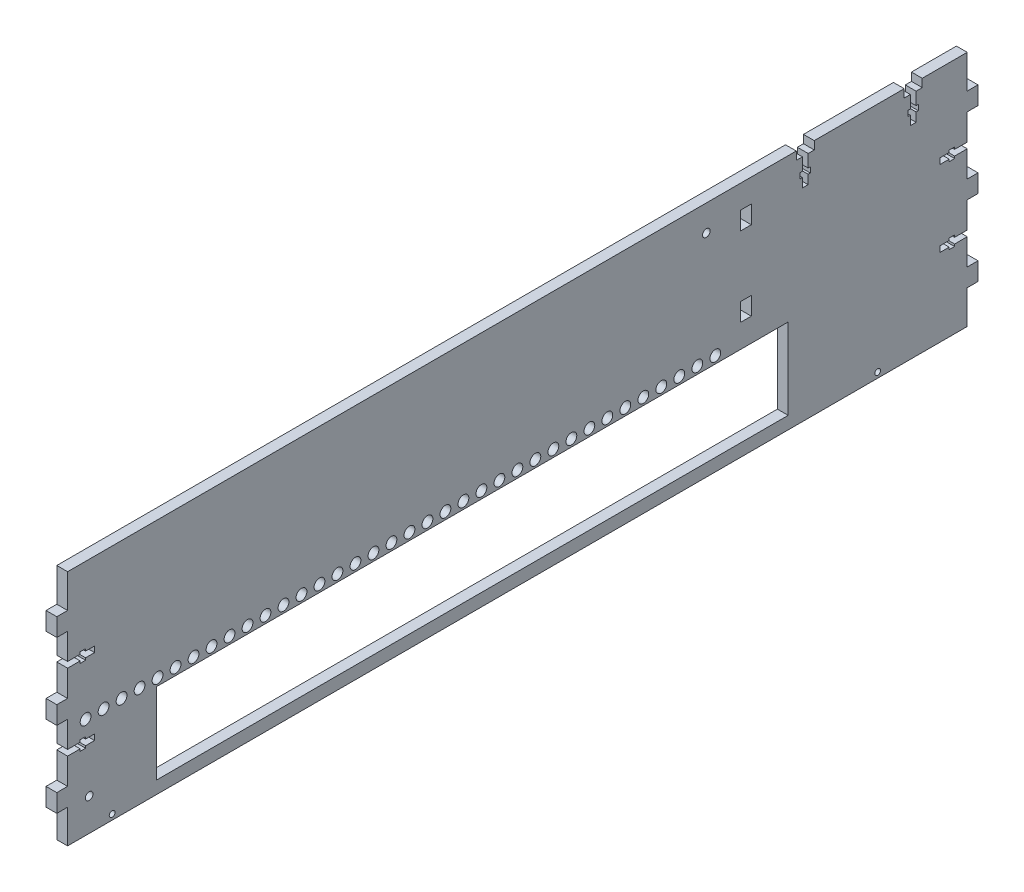
SolidWorks part; units mm, degrees
ref_plane "Front Plane" through (0, 0, 0) normal (0, 0, 1) x (1, 0, 0)
ref_plane "Top Plane" through (0, 0, 0) normal (0, 1, 0) x (1, 0, 0)
ref_plane "Right Plane" through (0, 0, 0) normal (1, 0, 0) x (0, 0, -1)
sketch "Sketch1" plane through (0, 0, 0) normal (1, 0, 0) x (0, 0, -1)
  line L1 (-250, -66) -> (250, -66)
  line L2 (-250, -66) -> (-250, 66)
  line L3 (-250, 66) -> (250, 66)
  line L4 (250, -66) -> (250, 66)
  line L5 (-250, -66) -> (250, 66) construction
  line L6 (-250, 66) -> (250, -66) construction
  point P0 (0, 0)
  dimension "D1" = 132
  dimension "D2" = 500
extrude "Boss-Extrude1" add sketch "Sketch1" along normal blind 6
sketch "Sketch4" plane through (0, 0, 250) normal (0, 0, 1) x (1, 0, 0)
  line L0 (0, 66) -> (0, -66) construction
  line L1 (0, 47.3321) -> (6, 47.3321)
  line L2 (0, 47.3321) -> (0, 37.3321)
  line L3 (0, 37.3321) -> (6, 37.3321)
  line L4 (6, 47.3321) -> (6, 37.3321)
  line L5 (6, 66) -> (6, -66) construction
  line L6 (0, 37.3321) -> (6, 37.3321) construction
  line L7 (0, -66) -> (0, 66) construction
  line L8 (6, 47.3321) -> (0, 47.3321) construction
  line L9 (0, -5) -> (6, -5) construction
  line L10 (0, -5) -> (6, -5)
  line L11 (0, -5) -> (0, 5)
  line L12 (0, 5) -> (6, 5)
  line L13 (6, -5) -> (6, 5)
  line L14 (6, -66) -> (6, 66) construction
  line L15 (6, 5) -> (0, 5) construction
  line L16 (6, -37.3321) -> (0, -37.3321) construction
  line L17 (0, -47.3321) -> (6, -47.3321)
  line L18 (0, -47.3321) -> (0, -37.3321)
  line L19 (0, -37.3321) -> (6, -37.3321)
  line L20 (6, -47.3321) -> (6, -37.3321)
  line L21 (0, -47.3321) -> (6, -47.3321) construction
extrude "Boss-Extrude2" add sketch "Sketch4" along normal blind 6
sketch "Sketch5" plane through (0, 0, 0) normal (-1, 0, 0) x (0, 0, 1)
  line L1 (250, 22.7661) -> (250, 19.5661) construction
  line L3 (250, 22.7661) -> (250, 19.5661) construction
  line L4 (250, -19.5661) -> (250, -22.7661) construction
  line L5 (250, -19.5661) -> (250, -22.7661) construction
  line L6 (250, 21.1661) -> (235, 21.1661) construction
  line L7 (250, -21.1661) -> (235, -21.1661) construction
  line L8 (250, -19.5661) -> (243, -19.5661)
  line L9 (250, 22.7661) -> (243, 22.7661)
  line L10 (250, -22.7661) -> (243, -22.7661)
  line L11 (250, 19.5661) -> (243, 19.5661)
  line L12 (250, -19.5661) -> (250, -22.7661)
  line L13 (235, -19.5661) -> (235, -22.7661)
  line L14 (250, 22.7661) -> (250, 19.5661)
  line L15 (235, 22.7661) -> (235, 19.5661)
  line L16 (240, 19.5661) -> (235, 19.5661)
  line L17 (243, 18.3661) -> (240, 18.3661)
  line L18 (243, 18.3661) -> (243, 19.5661)
  line L19 (243, 23.9661) -> (240, 23.9661)
  line L20 (240, 18.3661) -> (240, 19.5661)
  line L21 (243, 18.3661) -> (240, 23.9661) construction
  line L22 (243, 23.9661) -> (240, 18.3661) construction
  line L23 (243, -23.9661) -> (240, -23.9661)
  line L24 (243, -23.9661) -> (243, -22.7661)
  line L25 (243, -18.3661) -> (240, -18.3661)
  line L26 (240, -23.9661) -> (240, -22.7661)
  line L27 (243, -23.9661) -> (240, -18.3661) construction
  line L28 (243, -18.3661) -> (240, -23.9661) construction
  line L29 (250, 19.5661) -> (235, 19.5661) construction
  line L30 (243, 22.7661) -> (243, 23.9661)
  line L31 (240, 22.7661) -> (235, 22.7661)
  line L32 (250, 22.7661) -> (235, 22.7661) construction
  line L33 (240, 22.7661) -> (240, 23.9661)
  line L34 (240, -19.5661) -> (235, -19.5661)
  line L35 (250, -19.5661) -> (235, -19.5661) construction
  line L36 (240, -19.5661) -> (240, -18.3661)
  line L37 (240, -22.7661) -> (235, -22.7661)
  line L38 (250, -22.7661) -> (235, -22.7661) construction
  line L39 (243, -19.5661) -> (243, -18.3661)
  point P20 (241.5, 21.1661)
  point P25 (241.5, -21.1661)
  line M35 (250, -37.3321) -> (250, -5)
  line M39 (250, 5) -> (250, 37.3321)
  dimension "D3" = 1.6
  dimension "D4" = 7
  dimension "D5" = 3
  dimension "D6" = 5.6
  dimension "D1" = 15
  dimension "D7" = 7
  dimension "D8" = 3
  dimension "D9" = 5.6
  dimension "D2" = 1.6
extrude "Cut-Extrude3" cut sketch "Sketch5" against normal up to next contours L12 | L8 L39 L25 L36 L34 L13 L37 L26 L23 L24 L10 M35 | L33 L31 L15 L16 L20 L17 L18 L11 L9 L30 L19 M39 region at (0, -21.1661, 242.3696) region at (0, 21.1661, 242.3696)
sketch "Sketch6" plane through (0, 0, -250) normal (0, 0, -1) x (-1, 0, 0)
  line L0 (0, 47.3321) -> (0, 37.3321) construction
  line L1 (0, 37.3321) -> (-6, 37.3321) construction
  line L2 (-6, 37.3321) -> (-6, 47.3321) construction
  line L3 (-6, 47.3321) -> (0, 47.3321) construction
  line L4 (0, 5) -> (0, -5) construction
  line L5 (0, -5) -> (-6, -5) construction
  line L6 (-6, -5) -> (-6, 5) construction
  line L7 (-6, 5) -> (0, 5) construction
  line L8 (0, -37.3321) -> (0, -47.3321) construction
  line L9 (0, -47.3321) -> (-6, -47.3321) construction
  line L10 (-6, -47.3321) -> (-6, -37.3321) construction
  line L11 (-6, -37.3321) -> (0, -37.3321) construction
  line L12 (0, 47.3321) -> (0, 37.3321)
  line L13 (0, 37.3321) -> (-6, 37.3321)
  line L14 (-6, 37.3321) -> (-6, 47.3321)
  line L15 (-6, 47.3321) -> (0, 47.3321)
  line L16 (0, 5) -> (0, -5)
  line L17 (0, -5) -> (-6, -5)
  line L18 (-6, -5) -> (-6, 5)
  line L19 (-6, 5) -> (0, 5)
  line L20 (0, -37.3321) -> (0, -47.3321)
  line L21 (0, -47.3321) -> (-6, -47.3321)
  line L22 (-6, -47.3321) -> (-6, -37.3321)
  line L23 (-6, -37.3321) -> (0, -37.3321)
extrude "Boss-Extrude3" add sketch "Sketch6" along normal blind 6
sketch "Sketch7" plane through (0, 0, 0) normal (-1, 0, 0) x (0, 0, 1)
  line L0 (243, 19.5661) -> (250, 19.5661) construction
  line L2 (243, 19.5661) -> (243, 18.3661) construction
  line L3 (240, 18.3661) -> (243, 18.3661) construction
  line L4 (240, 19.5661) -> (240, 18.3661) construction
  line L5 (235, 19.5661) -> (240, 19.5661) construction
  line L6 (235, 19.5661) -> (235, 22.7661) construction
  line L7 (235, 22.7661) -> (240, 22.7661) construction
  line L8 (240, 23.9661) -> (240, 22.7661) construction
  line L9 (240, 23.9661) -> (243, 23.9661) construction
  line L10 (243, 23.9661) -> (243, 22.7661) construction
  line L11 (243, 22.7661) -> (250, 22.7661) construction
  line L12 (243, 19.5661) -> (250, 19.5661) construction
  line L13 (243, 19.5661) -> (243, 18.3661) construction
  line L14 (240, 18.3661) -> (243, 18.3661) construction
  line L15 (240, 19.5661) -> (240, 18.3661) construction
  line L16 (235, 19.5661) -> (240, 19.5661) construction
  line L17 (235, 19.5661) -> (235, 22.7661) construction
  line L18 (235, 22.7661) -> (240, 22.7661) construction
  line L19 (240, 23.9661) -> (240, 22.7661) construction
  line L20 (240, 23.9661) -> (243, 23.9661) construction
  line L21 (243, 23.9661) -> (243, 22.7661) construction
  line L22 (243, 22.7661) -> (250, 22.7661) construction
  line L23 (235, -22.7661) -> (240, -22.7661) construction
  line L24 (240, -22.7661) -> (240, -23.9661) construction
  line L25 (240, -23.9661) -> (243, -23.9661) construction
  line L26 (243, -22.7661) -> (243, -23.9661) construction
  line L27 (243, -22.7661) -> (250, -22.7661) construction
  line L28 (243, -19.5661) -> (250, -19.5661) construction
  line L29 (243, -18.3661) -> (243, -19.5661) construction
  line L30 (240, -18.3661) -> (243, -18.3661) construction
  line L31 (240, -18.3661) -> (240, -19.5661) construction
  line L32 (235, -19.5661) -> (240, -19.5661) construction
  line L33 (235, -22.7661) -> (235, -19.5661) construction
  line L34 (235, -22.7661) -> (240, -22.7661) construction
  line L35 (240, -22.7661) -> (240, -23.9661) construction
  line L36 (240, -23.9661) -> (243, -23.9661) construction
  line L37 (243, -22.7661) -> (243, -23.9661) construction
  line L38 (243, -22.7661) -> (250, -22.7661) construction
  line L39 (243, -19.5661) -> (250, -19.5661) construction
  line L40 (243, -18.3661) -> (243, -19.5661) construction
  line L41 (240, -18.3661) -> (243, -18.3661) construction
  line L42 (240, -18.3661) -> (240, -19.5661) construction
  line L43 (235, -19.5661) -> (240, -19.5661) construction
  line L44 (235, -22.7661) -> (235, -19.5661) construction
  line L45 (0, 0) -> (0, 57.5645) construction
  line L46 (-235, -22.7661) -> (-235, -19.5661)
  line L47 (-235, -19.5661) -> (-240, -19.5661)
  line L48 (-240, -18.3661) -> (-240, -19.5661)
  line L49 (-240, -18.3661) -> (-243, -18.3661)
  line L50 (-243, -18.3661) -> (-243, -19.5661)
  line L51 (-243, -19.5661) -> (-250, -19.5661)
  line L52 (-243, -22.7661) -> (-250, -22.7661)
  line L53 (-243, -22.7661) -> (-243, -23.9661)
  line L54 (-240, -23.9661) -> (-243, -23.9661)
  line L55 (-240, -22.7661) -> (-240, -23.9661)
  line L56 (-235, -22.7661) -> (-240, -22.7661)
  line L57 (-243, 22.7661) -> (-250, 22.7661)
  line L58 (-243, 23.9661) -> (-243, 22.7661)
  line L59 (-240, 23.9661) -> (-243, 23.9661)
  line L60 (-240, 23.9661) -> (-240, 22.7661)
  line L61 (-235, 22.7661) -> (-240, 22.7661)
  line L62 (-235, 19.5661) -> (-235, 22.7661)
  line L63 (-235, 19.5661) -> (-240, 19.5661)
  line L64 (-240, 19.5661) -> (-240, 18.3661)
  line L65 (-240, 18.3661) -> (-243, 18.3661)
  line L66 (-243, 19.5661) -> (-243, 18.3661)
  line L67 (-243, 19.5661) -> (-250, 19.5661)
  line L68 (-250, 22.7661) -> (-250, 19.5661)
  line L69 (-250, -19.5661) -> (-250, -22.7661)
extrude "Cut-Extrude4" cut sketch "Sketch7" against normal up to next
sketch "Sketch8" plane through (0, 0, 0) normal (-1, 0, 0) x (0, 0, 1)
  line L0 (200, -14.55) -> (-150, -14.55) construction
  line L1 (200, -14.55) -> (-150, -14.55) construction
  line L2 (200, -14.55) -> (200, -59) construction
  line L3 (200, -14.55) -> (200, -59) construction
  line L186 (-150, -14.55) -> (-150, -59) construction
  line L187 (-150, -59) -> (200, -59) construction
  line L188 (200.5, -14.05) -> (200.5, -59)
  line L189 (200.5, -14.05) -> (-150.5, -14.05)
  line L190 (-150.5, -14.05) -> (-150.5, -59)
  line L191 (-150.5, -59) -> (200.5, -59)
  dimension "D1" = 0.5
extrude "Cut-Extrude5" cut sketch "Sketch8" against normal up to next
sketch "Sketch11" plane through (6, 0, 0) normal (1, 0, 0) x (0, 0, -1)
  line L0 (130, 43) -> (130, 53) construction
  line L1 (130, 53) -> (124, 53) construction
  line L2 (124, 53) -> (124, 43) construction
  line L3 (124, 43) -> (130, 43) construction
  line L4 (130, -1) -> (130, 9) construction
  line L5 (130, 9) -> (124, 9) construction
  line L6 (124, 9) -> (124, -1) construction
  line L7 (124, -1) -> (130, -1) construction
  line L8 (130, 43) -> (130, 53)
  line L9 (130, 53) -> (124, 53)
  line L10 (124, 53) -> (124, 43)
  line L11 (124, 43) -> (130, 43)
  line L12 (130, -1) -> (130, 9)
  line L13 (130, 9) -> (124, 9)
  line L14 (124, 9) -> (124, -1)
  line L15 (124, -1) -> (130, -1)
extrude "Cut-Extrude8" cut sketch "Sketch11" against normal up to next
sketch "Sketch12" plane through (0, 0, 0) normal (-1, 0, 0) x (0, 0, 1)
  line L0 (-124, 53) -> (-124, 43) construction
  line L1 (-250, 66) -> (250, 66) construction
  circle A0 centre (-105, 51.5) radius 2.1
  dimension "D1" = 19
  dimension "D3" = 4.2
  dimension "D2" = 14.5
extrude "Cut-Extrude9" cut sketch "Sketch12" against normal up to next
sketch "Sketch13" plane through (0, 66, 0) normal (0, 1, 0) x (1, 0, 0)
  line L0 (6, 250) -> (6, -250) construction
  line L1 (0, 215) -> (6, 215)
  line L2 (0, 215) -> (0, 225)
  line L3 (0, 225) -> (6, 225)
  line L4 (6, 215) -> (6, 225)
  line L5 (0, 215) -> (6, 225) construction
  line L6 (0, 225) -> (6, 215) construction
  line L7 (6, 225) -> (0, 225) construction
  line L8 (6, 165) -> (0, 165) construction
  line L9 (0, 155) -> (6, 155)
  line L10 (0, 155) -> (0, 165)
  line L11 (0, 165) -> (6, 165)
  line L12 (6, 155) -> (6, 165)
  line L13 (0, 155) -> (6, 165) construction
  line L14 (0, 165) -> (6, 155) construction
  point P0 (3, 220)
  point P10 (3, 160)
extrude "Cut-Extrude10" cut sketch "Sketch13" against normal blind 4.5
sketch "Sketch14" plane through (0, 0, 0) normal (-1, 0, 0) x (0, 0, 1)
  circle A0 centre (240, -10) radius 3 construction
  circle A1 centre (240, -10) radius 3
  circle A2 centre (230, -10) radius 3
  circle A3 centre (220, -10) radius 3
  circle A4 centre (210, -10) radius 3
  circle A5 centre (200, -10) radius 3
  circle A6 centre (190, -10) radius 3
  circle A7 centre (180, -10) radius 3
  circle A8 centre (170, -10) radius 3
  circle A9 centre (160, -10) radius 3
  circle A10 centre (150, -10) radius 3
  circle A11 centre (140, -10) radius 3
  circle A12 centre (130, -10) radius 3
  circle A13 centre (120, -10) radius 3
  circle A14 centre (110, -10) radius 3
  circle A15 centre (100, -10) radius 3
  circle A16 centre (90, -10) radius 3
  circle A17 centre (80, -10) radius 3
  circle A18 centre (70, -10) radius 3
  circle A19 centre (60, -10) radius 3
  circle A20 centre (50, -10) radius 3
  circle A21 centre (40, -10) radius 3
  circle A22 centre (30, -10) radius 3
  circle A23 centre (20, -10) radius 3
  circle A24 centre (10, -10) radius 3
  circle A25 centre (0, -10) radius 3
  circle A26 centre (-10, -10) radius 3
  circle A27 centre (-20, -10) radius 3
  circle A28 centre (-30, -10) radius 3
  circle A29 centre (-40, -10) radius 3
  circle A30 centre (-50, -10) radius 3
  circle A31 centre (-60, -10) radius 3
  circle A32 centre (-70, -10) radius 3
  circle A33 centre (-80, -10) radius 3
  circle A34 centre (-90, -10) radius 3
  circle A35 centre (-100, -10) radius 3
  circle A36 centre (-110, -10) radius 3
  dimension "D1" = 36
extrude "Cut-Extrude11" cut sketch "Sketch14" against normal up to next (6 mm away)
sketch "Sketch15" plane through (6, 0, 0) normal (1, 0, 0) x (0, 0, -1)
  line L0 (160, 61.5) -> (160, 46.5) construction
  line L1 (155, 61.5) -> (165, 61.5) construction
  line L2 (220, 61.5) -> (220, 46.5) construction
  line L3 (215, 61.5) -> (225, 61.5) construction
  line L4 (160, 46.5) -> (220, 46.5) construction
  line L5 (190, 46.5) -> (190, 66) construction
  line L6 (215, 66) -> (165, 66) construction
  line L7 (158.4, 61.5) -> (158.4, 54.5)
  line L8 (161.6, 61.5) -> (161.6, 54.5)
  line L9 (158.4, 61.5) -> (161.6, 61.5)
  line L10 (158.4, 46.5) -> (161.6, 46.5)
  line L11 (161.6, 51.5) -> (162.8, 51.5)
  line L12 (157.2, 54.5) -> (158.4, 54.5)
  line L13 (157.2, 54.5) -> (157.2, 51.5)
  line L14 (157.2, 51.5) -> (158.4, 51.5)
  line L15 (162.8, 54.5) -> (162.8, 51.5)
  line L16 (157.2, 54.5) -> (162.8, 51.5) construction
  line L17 (157.2, 51.5) -> (162.8, 54.5) construction
  line L18 (161.6, 54.5) -> (162.8, 54.5)
  line L19 (158.4, 51.5) -> (158.4, 46.5)
  line L20 (158.4, 61.5) -> (158.4, 46.5) construction
  line L21 (161.6, 51.5) -> (161.6, 46.5)
  line L22 (161.6, 61.5) -> (161.6, 46.5) construction
  line L23 (222.8, 51.5) -> (217.2, 54.5) construction
  line L24 (222.8, 54.5) -> (217.2, 51.5) construction
  line L25 (220, 61.5) -> (220, 46.5) construction
  line L26 (218.4, 51.5) -> (218.4, 46.5)
  line L27 (221.6, 51.5) -> (221.6, 46.5)
  line L28 (218.4, 54.5) -> (217.2, 54.5)
  line L29 (217.2, 54.5) -> (217.2, 51.5)
  line L30 (222.8, 51.5) -> (221.6, 51.5)
  line L31 (222.8, 54.5) -> (222.8, 51.5)
  line L32 (222.8, 54.5) -> (221.6, 54.5)
  line L33 (218.4, 51.5) -> (217.2, 51.5)
  line L34 (221.6, 46.5) -> (218.4, 46.5)
  line L35 (221.6, 61.5) -> (218.4, 61.5)
  line L36 (218.4, 61.5) -> (218.4, 54.5)
  line L37 (221.6, 61.5) -> (221.6, 54.5)
  point P16 (160, 53)
  point P37 (220, 53)
  dimension "D3" = 15
  dimension "D4" = 7
  dimension "D5" = 3
  dimension "D6" = 5.6
  dimension "D1" = 1.6
  dimension "D2" = 1.6
extrude "Cut-Extrude12" cut sketch "Sketch15" against normal up to next
sketch "Sketch16" plane through (6, 0, 0) normal (1, 0, 0) x (0, 0, -1)
  line L0 (-250, -66) -> (250, -66) construction
  line L1 (-250, -66) -> (250, -66) construction
  line L2 (56.1704, -66) -> (56.1704, -51) construction
  line L3 (57.7704, -66) -> (57.7704, -59)
  line L4 (54.5704, -66) -> (54.5704, -59)
  line L5 (57.7704, -66) -> (54.5704, -66)
  line L6 (57.7704, -51) -> (54.5704, -51)
  line L7 (57.7704, -56) -> (57.7704, -51)
  line L8 (53.3704, -59) -> (54.5704, -59)
  line L9 (53.3704, -59) -> (53.3704, -56)
  line L10 (53.3704, -56) -> (54.5704, -56)
  line L11 (58.9704, -59) -> (58.9704, -56)
  line L12 (53.3704, -59) -> (58.9704, -56) construction
  line L13 (53.3704, -56) -> (58.9704, -59) construction
  line L14 (57.7704, -66) -> (57.7704, -51) construction
  line L15 (57.7704, -56) -> (58.9704, -56)
  line L16 (54.5704, -56) -> (54.5704, -51)
  line L17 (54.5704, -66) -> (54.5704, -51) construction
  line L18 (57.7704, -59) -> (58.9704, -59)
  line L19 (-250, -66) -> (250, -66) construction
  line L20 (-250, -66) -> (250, -66) construction
  line L21 (56.1704, -66) -> (56.1704, -51) construction
  line L22 (57.7704, -66) -> (57.7704, -59)
  line L23 (54.5704, -66) -> (54.5704, -59)
  line L24 (57.7704, -66) -> (54.5704, -66)
  line L25 (57.7704, -51) -> (54.5704, -51)
  line L26 (57.7704, -59) -> (58.9704, -59)
  line L27 (53.3704, -59) -> (54.5704, -59)
  line L28 (53.3704, -59) -> (53.3704, -56)
  line L29 (53.3704, -56) -> (54.5704, -56)
  line L30 (58.9704, -59) -> (58.9704, -56)
  line L31 (53.3704, -59) -> (58.9704, -56) construction
  line L32 (53.3704, -56) -> (58.9704, -59) construction
  line L33 (57.7704, -56) -> (57.7704, -51)
  line L34 (57.7704, -66) -> (57.7704, -51) construction
  line L35 (57.7704, -56) -> (58.9704, -56)
  line L36 (54.5704, -56) -> (54.5704, -51)
  line L37 (54.5704, -66) -> (54.5704, -51) construction
  point P8 (56.1704, -57.5)
  point P25 (56.1704, -57.5)
  dimension "D1" = 15
  dimension "D4" = 7
  dimension "D5" = 3
  dimension "D6" = 5.6
  dimension "D2" = 1.6
  dimension "D3" = 1.6
  dimension "D7" = 1.6
  dimension "D8" = 1.6
sketch "Sketch17" plane through (6, 0, 0) normal (1, 0, 0) x (0, 0, -1)
  circle A0 centre (-238, -48) radius 2.1 construction
  circle A1 centre (-238, -48) radius 2.1
extrude "Cut-Extrude14" cut sketch "Sketch17" against normal through all
sketch "Sketch18" plane through (6, 0, 0) normal (1, 0, 0) x (0, 0, -1)
  line L0 (-200.5, -59) -> (-250, -59) construction
  line L1 (-250, -47.3321) -> (-250, -66) construction
  line L2 (-225.25, -59) -> (-225.25, -66) construction
  line L3 (-250, -66) -> (250, -66) construction
  line L4 (150.5, -59) -> (250, -59) construction
  line L5 (250, -66) -> (250, -47.3321) construction
  line L6 (200.25, -59) -> (200.25, -66) construction
  circle A0 centre (-225.25, -63) radius 1.6
  circle A1 centre (200.25, -63) radius 1.6
  point P20 (0, 0)
  dimension "D1" = 3.2
  dimension "D2" = 3
extrude "Cut-Extrude15" cut sketch "Sketch18" against normal through all
